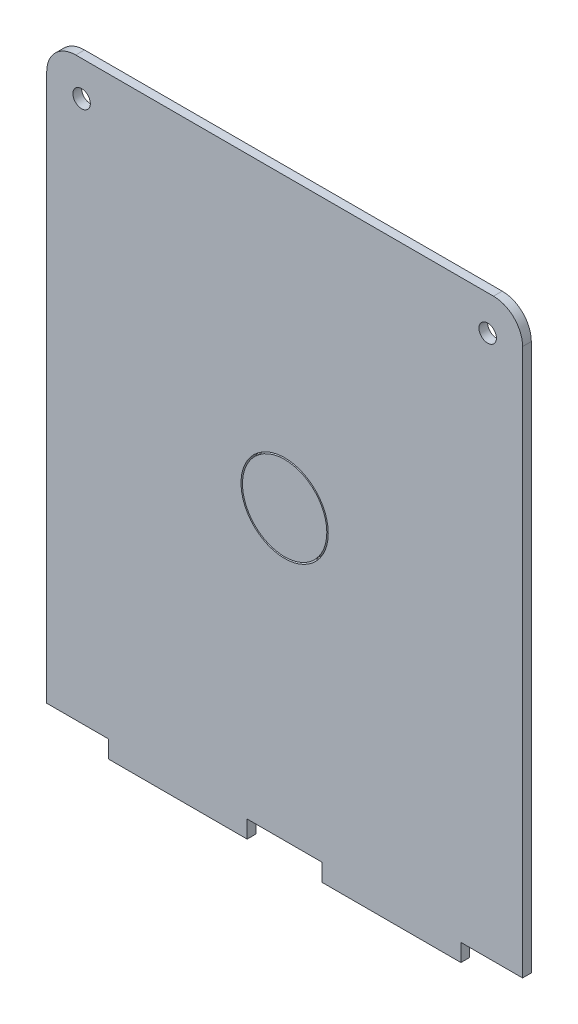
SolidWorks part; units mm, degrees
ref_plane "Front Plane" through (0, 0, 0) normal (0, 0, 1) x (1, 0, 0)
ref_plane "Top Plane" through (0, 0, 0) normal (0, 1, 0) x (1, 0, 0)
ref_plane "Right Plane" through (0, 0, 0) normal (1, 0, 0) x (0, 0, -1)
sketch "Sketch1" plane through (0, 0, 0) normal (0, 0, 1) x (1, 0, 0)
  line L1 (0, 0) -> (81.8, 0)
  line L2 (0, 0) -> (0, 102)
  line L3 (0, 102) -> (81.8, 102)
  line L4 (81.8, 0) -> (81.8, 102)
  dimension "D1" = 81.8
  dimension "D2" = 102
extrude "Boss-Extrude1" add sketch "Sketch1" along normal blind 1.5
sketch "Sketch2" plane through (0, 0, 1.5) normal (0, 0, 1) x (1, 0, 0)
  line L0 (40.9, 102) -> (40.9, 0)
  line L1 (81.8, 102) -> (0, 102) construction
  line L2 (0, 0) -> (81.8, 0) construction
  line L3 (81.8, 0) -> (81.8, 3)
  line L4 (0, 0) -> (10.6, 0)
  line L5 (0, 0) -> (0, 3)
  line L6 (0, 3) -> (10.6, 3)
  line L7 (10.6, 0) -> (10.6, 3)
  line L8 (34.455, 0) -> (47.345, 0)
  line L9 (34.455, 0) -> (34.455, 3)
  line L10 (34.455, 3) -> (47.345, 3)
  line L11 (47.345, 0) -> (47.345, 3)
  line L12 (81.8, 0) -> (71.2, 0)
  line L13 (71.2, 0) -> (71.2, 3)
  line L14 (81.8, 3) -> (71.2, 3)
  line L15 (0, 102) -> (0, 0) construction
  circle A0 centre (6, 96) radius 1.5
  circle A1 centre (75.8, 96) radius 1.5
  line M8 (0, 102) -> (0, 0)
  line M9 (0, 0) -> (81.8, 0)
  line M10 (81.8, 0) -> (81.8, 102)
  dimension "D5" = 6
  dimension "D1" = 3
  dimension "D2" = 10.6
  dimension "D3" = 12.89
  dimension "D4" = 6.445
  dimension "D6" = 6
extrude "Cut-Extrude1" cut sketch "Sketch2" against normal through all contours L7 L6 M9 M8 | L11 L10 L0 M9 | L10 L9 L0 M9 | L14 L13 M10 M9 | A0 | A1 region at (44.1225, 1.5, 1.5) region at (37.6775, 1.5, 1.5) region at (76.5, 1.5, 1.5) region at (5.3, 1.5, 1.5)
sketch "Sketch3" plane through (0, 0, 1.5) normal (0, 0, 1) x (1, 0, 0)
  line L0 (0, 33.6536) -> (81.8, 33.6536)
  line L1 (0, 102) -> (0, 3) construction
  line L2 (81.8, 3) -> (81.8, 102) construction
  line L3 (40.9, 102) -> (40.9, 3)
  line L4 (81.8, 102) -> (0, 102) construction
  line L5 (34.455, 3) -> (47.345, 3) construction
  line L6 (35.4, 39.1536) -> (46.4, 39.1536)
  line L7 (35.4, 28.1536) -> (46.4, 28.1536)
  circle A0 centre (35.4, 33.6536) radius 5.5
  circle A1 centre (46.4, 33.6536) radius 5.5
  point P19 (40.9, 28.1536)
  point P20 (40.9, 39.1536)
  dimension "D1" = 5.5
  dimension "D2" = 11
  dimension "D3" = 68.3464
extrude "Cut-Extrude2" [suppressed] cut sketch "Sketch3" against normal through all contours L0 A0 | L0 A0 | A1 L0 | A1 L0 | A0 L7 L3 | L7 A1 L3 | L3 A1 L6 | A0 L3 L6
fillet "Fillet1" radius 5 2 edges at (81.8, 102, 0.75) (0, 102, 0.75)
sketch "Sketch4" plane through (0, 0, 1.5) normal (0, 0, 1) x (1, 0, 0)
  line L0 (40.9, 102) -> (40.9, 3)
  line L1 (76.8, 102) -> (5, 102) construction
  line L2 (34.455, 3) -> (47.345, 3) construction
  circle A0 centre (40.9, 52.5) radius 7.5
  circle A1 centre (40.9, 52.5) radius 7.25
  dimension "D1" = 15
extrude "Cut-Extrude3" cut sketch "Sketch4" against normal blind 10 contours L0 A0 | L0 A0 region at (46.0847, 57.6847, 1.5) region at (40.7323, 59.875, 1.5)
